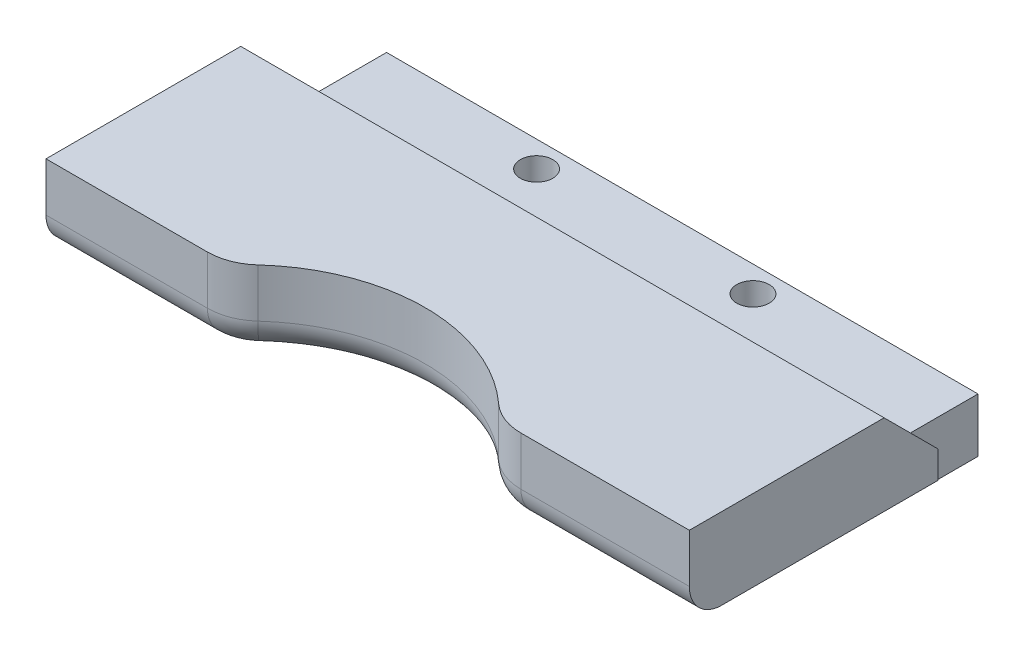
SolidWorks part; units mm, degrees
ref_plane "Front Plane" through (0, 0, 0) normal (0, 0, 1) x (1, 0, 0)
ref_plane "Top Plane" through (0, 0, 0) normal (0, 1, 0) x (1, 0, 0)
ref_plane "Right Plane" through (0, 0, 0) normal (1, 0, 0) x (0, 0, -1)
sketch "草图1" plane through (0, 0, 0) normal (0, 1, 0) x (1, 0, 0)
  line L0 (0, 0) -> (0, -9.0163) construction
  line L1 (0, 0) -> (-22.0911, 0) construction
  line L3 (-26.2566, -6.11) -> (28.4077, -6.11)
  line L4 (-26.2566, -6.11) -> (-26.2566, -11.11)
  line L5 (-26.2566, -11.11) -> (28.4077, -11.11)
  line L6 (28.4077, -6.11) -> (28.4077, -11.11)
  circle A0 centre (-10, -8.5) radius 1.5
  circle A1 centre (10, -8.5) radius 1.5
  dimension "D1" = 3
  dimension "D2" = 8.5
  dimension "D3" = 10
  dimension "D4" = 2.61
  dimension "D5" = 5
extrude "凸台-拉伸1" add sketch "草图1" along normal blind 5 contours L4 L3 L6 L5 | A0 | A1
sketch "草图2" plane through (0, 0, 11.11) normal (0, 0, 1) x (1, 0, 0)
  line L0 (0, 0) -> (0, 5) construction
  line L1 (-26.2566, 5) -> (28.4077, 5) construction
  line L3 (-29.7301, 3.7502) -> (29.7301, 3.7502)
  line L4 (-29.7301, 3.7502) -> (-29.7301, 1.2498)
  line L5 (-29.7301, 1.2498) -> (29.7301, 1.2498)
  line L6 (29.7301, 3.7502) -> (29.7301, 1.2498)
  line L7 (-29.7301, 3.7502) -> (29.7301, 1.2498) construction
  line L8 (-29.7301, 1.2498) -> (29.7301, 3.7502) construction
  point P5 (0, 2.5)
extrude "凸台-拉伸2" add sketch "草图2" along normal blind 23
fillet "圆角1" [suppressed] radius 2
sketch "草图5" plane through (0, 3.7502, 0) normal (0, 1, 0) x (1, 0, 0)
  circle A0 centre (-0.32, -44.9941) radius 16.5
  dimension "D1" = 33
extrude "切除-拉伸1" cut sketch "草图5" against normal blind 15
fillet "圆角2" [suppressed] radius 3
sketch "草图6" plane through (0, 3.7502, 0) normal (0, 1, 0) x (1, 0, 0)
  line L4 (29.7301, -11.11) -> (28.4077, -11.11)
  line L6 (-29.7301, -11.11) -> (-29.7301, -34.11)
  line L7 (-29.7301, -11.11) -> (-29.7301, -34.11)
  line L8 (-29.7301, -34.11) -> (-12.721, -34.11)
  line L9 (-29.7301, -34.11) -> (-12.721, -34.11)
  line L10 (29.7301, -34.11) -> (29.7301, -11.11)
  line L22 (29.7301, -34.11) -> (29.7301, -11.11)
  line L23 (29.7301, -11.11) -> (28.4077, -11.11)
  line L25 (28.4077, -11.11) -> (-26.2566, -11.11)
  line L26 (28.4077, -11.11) -> (-26.2566, -11.11)
  line L27 (12.081, -34.11) -> (29.7301, -34.11)
  line L28 (12.081, -34.11) -> (29.7301, -34.11)
  line L30 (-26.2566, -11.11) -> (-29.7301, -11.11)
  line L31 (-26.2566, -11.11) -> (-29.7301, -11.11)
  arc A11 (12.081, -34.11) -> (-12.721, -34.11) centre (-0.32, -44.9941) ccw
  arc A12 (12.081, -34.11) -> (-12.721, -34.11) centre (-0.32, -44.9941) ccw
  dimension "D1" = 0
fillet "圆角3" [suppressed] radius 3
sketch "草图7" plane through (0, 3.7502, 0) normal (0, 1, 0) x (1, 0, 0)
  line L7 (-29.7301, -34.11) -> (-12.721, -34.11)
  line L8 (-29.7301, -34.11) -> (-12.721, -34.11)
  line L9 (29.7301, -34.11) -> (29.7301, -11.11)
  line L10 (29.7301, -11.11) -> (28.4077, -11.11)
  line L11 (28.4077, -11.11) -> (-26.2566, -11.11)
  line L12 (29.7301, -11.11) -> (28.4077, -11.11)
  line L13 (-29.7301, -11.11) -> (-29.7301, -34.11)
  line L16 (29.7301, -34.11) -> (29.7301, -11.11)
  line L18 (28.4077, -11.11) -> (-26.2566, -11.11)
  line L20 (-29.7301, -11.11) -> (-29.7301, -34.11)
  line L22 (12.081, -34.11) -> (29.7301, -34.11)
  line L23 (12.081, -34.11) -> (29.7301, -34.11)
  line L24 (-26.2566, -11.11) -> (-29.7301, -11.11)
  line L25 (-26.2566, -11.11) -> (-29.7301, -11.11)
  arc A7 (12.081, -34.11) -> (-12.721, -34.11) centre (-0.32, -44.9941) ccw
  arc A21 (12.081, -34.11) -> (-12.721, -34.11) centre (-0.32, -44.9941) ccw
  dimension "D1" = 0
extrude "凸台-拉伸3" add sketch "草图7" along normal blind 5
fillet "圆角4" [suppressed] radius 5
chamfer "倒角1" distance 5 angle 45 1 edges at (0, 8.7502, 11.11)
fillet "圆角5" [suppressed] radius 10
fillet "圆角6" radius 10 1 edges at (1.0755, 1.2498, 11.11)
sketch "草图8" plane through (0, 8.7502, 0) normal (0, 1, 0) x (1, 0, 0)
  line L0 (29.7301, -16.11) -> (-29.7301, -16.11) construction
  line L1 (-8.9381, -16.11) -> (9.4175, -16.11)
  line L2 (-8.9381, -16.11) -> (-8.9381, -19.3067)
  line L3 (-8.9381, -19.3067) -> (9.4175, -19.3067)
  line L4 (9.4175, -16.11) -> (9.4175, -19.3067)
extrude "凸台-拉伸4" [suppressed] add sketch "草图8" along normal blind 10
fillet "圆角7" radius 5 2 edges at (12.081, 5, 34.11) (-12.721, 5, 34.11)
fillet "圆角8" radius 3 5 edges at (21.9498, 1.2498, 34.11) (12.3625, 1.2498, 33.7721) (-22.2698, 1.2498, 34.11) (-13.0025, 1.2498, 33.7721) (-0.32, 1.2498, 28.4941)
